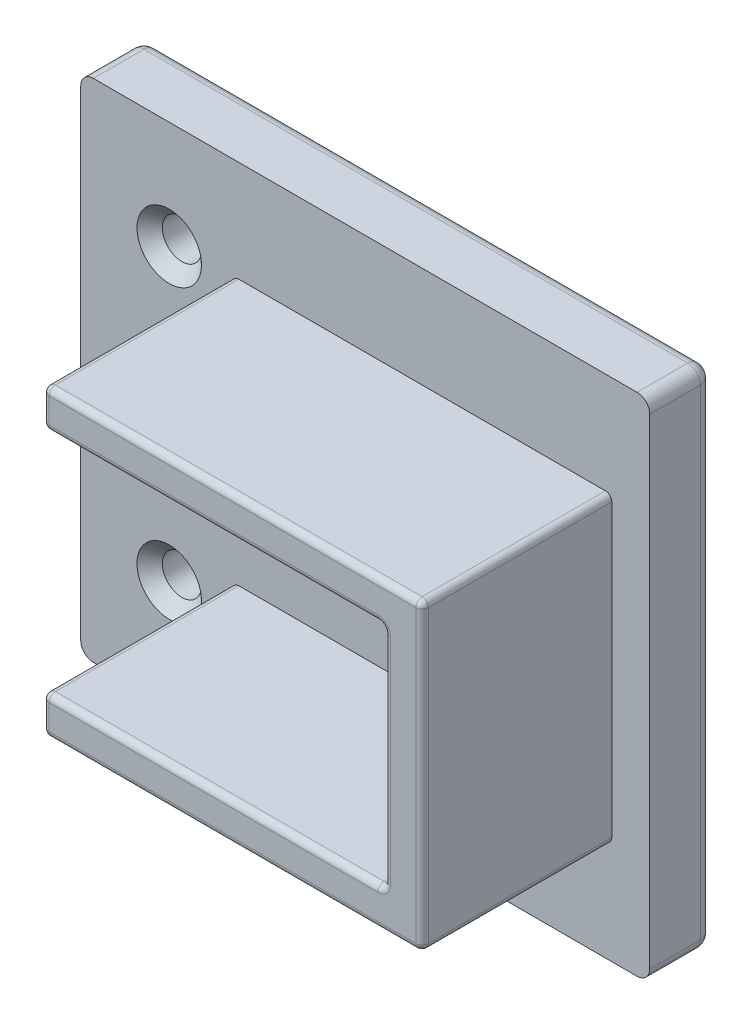
SolidWorks part; units mm, degrees
ref_plane "前视基准面" through (0, 0, 0) normal (0, 0, 1) x (1, 0, 0)
ref_plane "上视基准面" through (0, 0, 0) normal (0, 1, 0) x (1, 0, 0)
ref_plane "右视基准面" through (0, 0, 0) normal (1, 0, 0) x (0, 0, -1)
other "Configuration Table"
sketch "草图2" plane through (0, 0, 0) normal (0, 0, 1) x (1, 0, 0)
  line L1 (25, 20) -> (-20, 20)
  line L2 (25, 20) -> (25, -20)
  line L3 (25, -20) -> (-20, -20)
  line L4 (-20, 20) -> (-20, -20)
  line L5 (88, 0) -> (-32, 0) construction
  dimension "D1" = 40
  dimension "D2" = 45
  dimension "D3" = 25
extrude "凸台-拉伸1" add sketch "草图2" along normal blind 5
sketch "草图5" plane through (0, -20, 0) normal (0, -1, 0) x (1, 0, 0)
  line L0 (22, 5) -> (22, 20)
  line L1 (-20, 5) -> (25, 5) construction
  line L2 (22, 20) -> (-8, 20)
  line L3 (-8, 20) -> (-8, 5)
  line L4 (-8, 5) -> (22, 5)
  line L5 (25, 5) -> (25, 0) construction
  dimension "D1" = 30
  dimension "D2" = 15
  dimension "D4" = 3
extrude "凸台-拉伸2" add sketch "草图5" against normal blind 3 from offset 8 offset against normal yes
sketch "草图6" plane through (0, 20, 0) normal (0, 1, 0) x (1, 0, 0)
  line L4 (22, -20) -> (22, -5)
  line L5 (-8, -20) -> (22, -20)
  line L6 (-8, -5) -> (-8, -20)
  line L7 (22, -5) -> (-8, -5)
  line L8 (22, -20) -> (22, -5)
  line L9 (-8, -20) -> (22, -20)
  line L10 (-8, -5) -> (-8, -20)
  line L11 (22, -5) -> (-8, -5)
  dimension "D1" = 0
extrude "凸台-拉伸3" add sketch "草图6" against normal blind 3 from offset 8 offset against normal yes
sketch "草图7" plane through (0, 0, 0) normal (0, 0, -1) x (-1, 0, 0)
  line L0 (0, 0) -> (-49464.6492, 0) construction
  circle A4 centre (-12, 0) radius 1.55
  circle A5 centre (13, -11.5) radius 1.55
  circle A6 centre (13, 11.5) radius 1.55
  dimension "D1" = 3.1
  dimension "D2" = 25
  dimension "D3" = 11.5
  dimension "D4" = 11.5
  dimension "D5" = 12
extrude "切除-拉伸1" cut sketch "草图7" against normal up to next
sketch "草图8" plane through (22, 0, 0) normal (1, 0, 0) x (0, 0, -1)
  line L1 (-20, 9) -> (-5, 9)
  line L2 (-20, 9) -> (-20, -12)
  line L3 (-20, -12) -> (-5, -12)
  line L4 (-5, 9) -> (-5, -12)
extrude "凸台-拉伸4" add sketch "草图8" against normal blind 3
fillet "圆角4" radius 0.5 16 edges at (5.5, 9, 20) (-8, 10.5, 20) (7, 12, 20) (22, 0, 20) (7, -12, 20) (-8, -10.5, 20) (5.5, -9, 20) (19, 0, 20) (19, -9, 12.5) (-8, -9, 12.5) (-8, -12, 12.5) (22, 12, 12.5) (-8, 12, 12.5) (-8, 9, 12.5) (19, 9, 12.5) (22, -12, 12.5)
chamfer "倒角1" distance 1 angle 45 6 edges at (-14.55, 11.5, 5) (-14.55, 11.5, 0) (-14.55, -11.5, 5) (-14.55, -11.5, 0) (10.45, 0, 5) (10.45, 0, 0)
fillet "圆角3" radius 1 11 edges at (-20, -20, 2.5) (-20, 20, 2.5) (25, 20, 2.5) (25, -20, 2.5) (2.5, 20, 0) (-20, 0, 0) (2.5, -20, 0) (25, 0, 0) (9.45, 0, 0) (-15.55, -11.5, 0) (-15.55, 11.5, 0)
